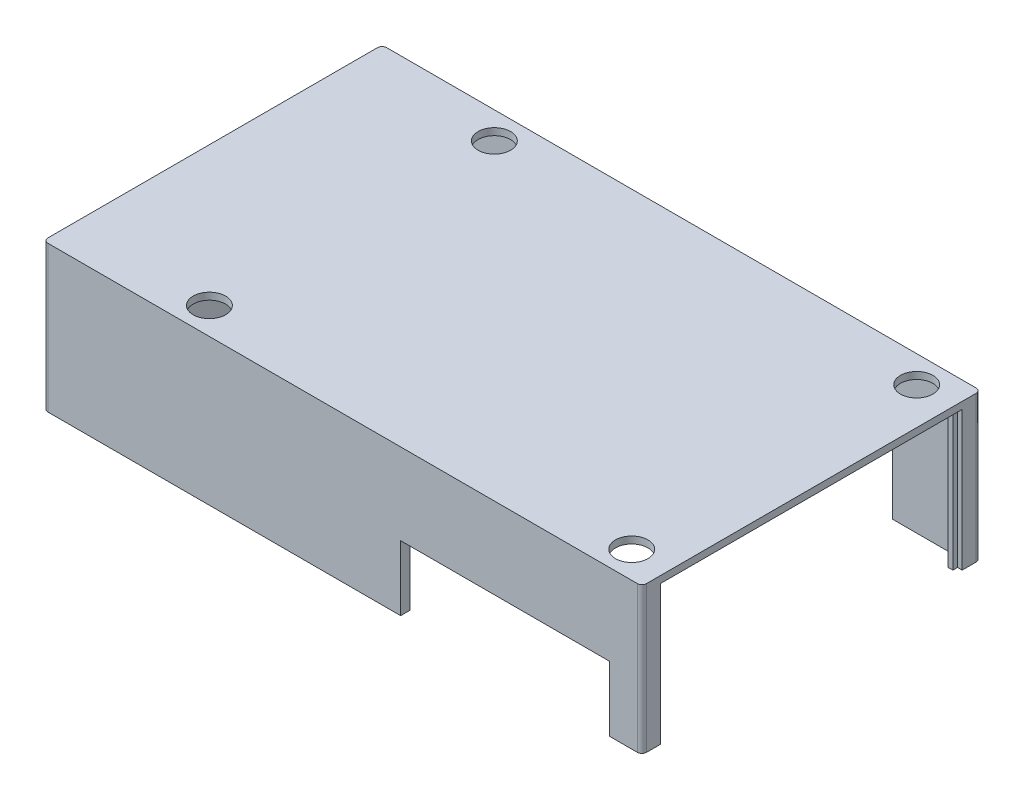
SolidWorks part; units mm, degrees
ref_plane "前视基准面" through (0, 0, 0) normal (0, 0, 1) x (1, 0, 0)
ref_plane "上视基准面" through (0, 0, 0) normal (0, 1, 0) x (1, 0, 0)
ref_plane "右视基准面" through (0, 0, 0) normal (1, 0, 0) x (0, 0, -1)
other "Configuration Table"
sketch "草图2" plane through (0, 0, 0) normal (0, 1, 0) x (1, 0, 0)
  line L0 (0, 0) -> (0, 3.0728) construction
  line L3 (-64.5, -34.5) -> (-62.5, -34.5)
  line L4 (-64.5, -34.5) -> (-64.5, 34.5)
  line L5 (-64.5, 34.5) -> (-62.5, 34.5)
  line L6 (-62.5, -34.5) -> (-62.5, 34.5)
  line L9 (0, 0) -> (3.0897, 0) construction
  line L10 (-64.5, -34.5) -> (64.5, -34.5)
  line L11 (-64.5, -34.5) -> (-64.5, -36.5)
  line L12 (-64.5, -36.5) -> (64.5, -36.5)
  line L13 (64.5, -34.5) -> (64.5, -36.5)
  line L15 (-64.5, 34.5) -> (64.5, 34.5)
  line L16 (-64.5, 34.5) -> (-64.5, 36.5)
  line L17 (-64.5, 36.5) -> (64.5, 36.5)
  line L18 (64.5, 34.5) -> (64.5, 36.5)
  line L19 (-64.5, 36.5) -> (64.5, 36.5)
  line L20 (62.5, 34.5) -> (64.5, 34.5)
  line L21 (62.5, 34.5) -> (62.5, -34.5)
  line L22 (62.5, -34.5) -> (64.5, -34.5)
  line L23 (64.5, 34.5) -> (64.5, -34.5)
  line L24 (-64.5, 36.5) -> (-64.5, -36.5)
  line L25 (-64.5, -36.5) -> (64.5, -36.5)
  line L26 (64.5, 36.5) -> (64.5, -36.5)
  point P0 (-62.5, 0)
  dimension "D1" = 69
  dimension "D2" = 2
  dimension "D3" = 62.5
  dimension "D4" = 2
  dimension "D5" = 3.0728
  dimension "D6" = 3.0897
  dimension "D7" = 129
  dimension "D8" = 2
  dimension "D9" = 129
  dimension "D10" = 2
  dimension "D11" = 69
extrude "凸台-拉伸1" add sketch "草图2" along normal blind 1.5 contours L24 L25 L26 L19
extrude "凸台-拉伸2" add sketch "草图2<4>" against normal blind 30 contours L6 L5 L4 L3
sketch "草图2<4>" plane through (0, 0, 0) normal (0, 1, 0) x (1, 0, 0) same geometry as "草图2"
extrude "凸台-拉伸3" add sketch "草图2<5>" against normal blind 30 contours L16 L15 L18 L17
sketch "草图2<5>" plane through (0, 0, 0) normal (0, 1, 0) x (1, 0, 0) same geometry as "草图2"
extrude "凸台-拉伸4" add sketch "草图2<6>" against normal blind 30 contours L12 L13 L10 L11
sketch "草图2<6>" plane through (0, 0, 0) normal (0, 1, 0) x (1, 0, 0) same geometry as "草图2"
sketch "草图4" plane through (0, -30, 0) normal (0, -1, 0) x (1, 0, 0)
  line L0 (-64.5, 34.5) -> (-64.5, -34.5) construction
  line L1 (-64.5, 15) -> (-63.5, 15)
  line L2 (-64.5, 15) -> (-64.5, -15)
  line L3 (-64.5, -15) -> (-63.5, -15)
  line L4 (-63.5, 15) -> (-63.5, -15)
  line L5 (-62.5, 34.5) -> (-62.5, -34.5) construction
  line L6 (0, 0) -> (-70, 0) construction
  line L7 (-64.5, -36.5) -> (64.5, -36.5) construction
  line L8 (-4.5, -36.5) -> (-14.5, -36.5)
  line L9 (-4.5, -36.5) -> (-4.5, -35.5)
  line L10 (-4.5, -35.5) -> (-14.5, -35.5)
  line L11 (-14.5, -36.5) -> (-14.5, -35.5)
  line L12 (-64.5, -34.5) -> (-64.5, -36.5) construction
  line L13 (-64.5, -34.5) -> (64.5, -34.5) construction
  line L14 (-14.5, 36.5) -> (-14.5, 35.5)
  line L15 (-4.5, 36.5) -> (-14.5, 36.5)
  line L16 (-4.5, 36.5) -> (-4.5, 35.5)
  line L17 (-4.5, 35.5) -> (-14.5, 35.5)
  line L23 (62.5, -34.5) -> (62.5, 34.5) construction
  line L24 (64.5, -34.5) -> (63.5, -34.5)
  line L25 (64.5, -34.5) -> (64.5, -35.5)
  line L26 (64.5, -35.5) -> (63.5, -35.5)
  line L27 (63.5, -34.5) -> (63.5, -35.5)
  line L28 (63.5, 34.5) -> (63.5, 35.5)
  line L29 (64.5, 35.5) -> (63.5, 35.5)
  line L30 (64.5, 34.5) -> (64.5, 35.5)
  line L31 (64.5, 34.5) -> (63.5, 34.5)
  dimension "D1" = 1
  dimension "D2" = 70
  dimension "D3" = 15
  dimension "D4" = 30
  dimension "D5" = 60
  dimension "D6" = 10
  dimension "D7" = 1
  dimension "D8" = 1
  dimension "D9" = 1
sketch "草图5" plane through (0, -30, 0) normal (0, -1, 0) x (1, 0, 0)
  line L0 (-64.5, 36.5) -> (64.5, 36.5) construction
  line L1 (57.5, 36.5) -> (12.5, 36.5)
  line L2 (57.5, 36.5) -> (57.5, 34.5)
  line L3 (57.5, 34.5) -> (12.5, 34.5)
  line L4 (12.5, 36.5) -> (12.5, 34.5)
  line L5 (-64.5, 34.5) -> (64.5, 34.5) construction
  line L6 (62.5, -34.5) -> (62.5, 34.5) construction
  dimension "D1" = 5
  dimension "D2" = 50
extrude "切除-拉伸2" cut sketch "草图5" against normal blind 14
sketch "草图6" plane through (0, -30, 0) normal (0, -1, 0) x (1, 0, 0)
  line L0 (-64.5, -34.5) -> (64.5, -34.5) construction
  line L1 (47.5, -34.5) -> (27.5, -34.5)
  line L2 (47.5, -34.5) -> (47.5, -36.5)
  line L3 (47.5, -36.5) -> (27.5, -36.5)
  line L4 (27.5, -34.5) -> (27.5, -36.5)
  line L5 (-64.5, -36.5) -> (64.5, -36.5) construction
  line L6 (-62.5, 34.5) -> (-62.5, -34.5) construction
  dimension "D1" = 90
  dimension "D2" = 110
extrude "切除-拉伸3" cut sketch "草图6" against normal blind 14
fillet "圆角1" radius 1 1 edges at (-64.5, -14.25, -36.5)
fillet "圆角2" radius 1 1 edges at (-64.5, -14.25, 36.5)
fillet "圆角5" radius 1 1 edges at (64.5, -14.25, 36.5)
sketch "草图8" plane through (0, 1.5, 0) normal (0, 1, 0) x (1, 0, 0)
  line L0 (-64.5, 35.5) -> (-64.5, -35.5) construction
  line L1 (-63.5, 36.5) -> (64.5, 36.5) construction
  line L2 (-63.5, -36.5) -> (63.5, -36.5) construction
  circle A0 centre (-34.5, 30.7) radius 3.5
  circle A1 centre (56.5, 30.7) radius 3.5
  circle A2 centre (-34.5, -30.7) radius 3.5
  circle A3 centre (56.5, -30.7) radius 3.5
  dimension "D1" = 7
  dimension "D4" = 91
  dimension "D5" = 7
  dimension "D6" = 5.8
  dimension "D7" = 7
  dimension "D8" = 7
  dimension "D2" = 30
  dimension "D3" = 5.8
extrude "切除-拉伸4" cut sketch "草图8" against normal blind 10
fillet "圆角6" radius 1 1 edges at (64.5, -14.25, -36.5)
sketch "草图9" plane through (0, 0, 0) normal (0, -1, 0) x (1, 0, 0)
  line L0 (0, 0) -> (100, 0) construction
  line L11 (-62.5, 34.5) -> (64.5, 34.5) construction
  line L12 (62.5, 34.5) -> (64.5, 34.5)
  line L20 (62.5, 31.5) -> (63.5, 31.5)
  line L21 (63.5, 31.5) -> (63.5, 32.5)
  line L22 (63.5, 32.5) -> (64.5, 32.5)
  line L23 (64.5, 34.5) -> (64.5, 32.5)
  line L24 (62.5, 34.5) -> (62.5, 31.5)
  line L25 (62.5, -34.5) -> (62.5, -31.5)
  line L26 (64.5, -34.5) -> (64.5, -32.5)
  line L27 (63.5, -32.5) -> (64.5, -32.5)
  line L28 (63.5, -31.5) -> (63.5, -32.5)
  line L29 (62.5, -31.5) -> (63.5, -31.5)
  line L30 (62.5, -34.5) -> (64.5, -34.5)
  dimension "D1" = 2
  dimension "D2" = 1
  dimension "D3" = 1
  dimension "D4" = 2
  dimension "D5" = 100
extrude "凸台-拉伸5" add sketch "草图9" along normal blind 30
